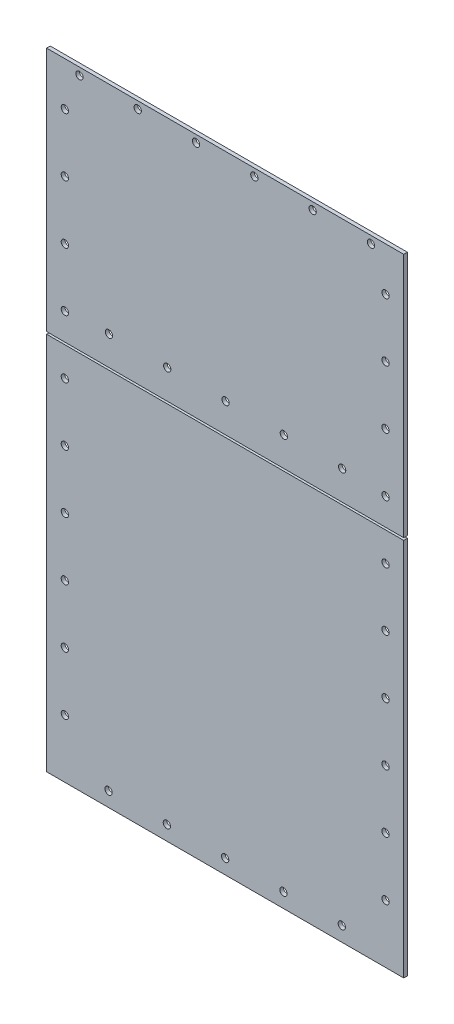
SolidWorks part; units mm, degrees
material "Copper"
ref_plane "Front Plane" through (0, 0, 0) normal (0, 0, 1) x (1, 0, 0)
ref_plane "Top Plane" through (0, 0, 0) normal (0, 1, 0) x (1, 0, 0)
ref_plane "Right Plane" through (0, 0, 0) normal (1, 0, 0) x (0, 0, -1)
sketch "Sketch1" plane through (0, 0, 0) normal (0, 0, 1) x (1, 0, 0)
  line L0 (0, -106.95) -> (155.58, -106.95)
  line L1 (0, 0) -> (155.58, 0)
  line L2 (0, 0) -> (0, -273.05)
  line L3 (0, -273.05) -> (155.58, -273.05)
  line L4 (155.58, 0) -> (155.58, -273.05)
  line L5 (0, -107.95) -> (155.58, -107.95)
  circle A0 centre (7.94, -19.05) radius 1.5875
  circle A1 centre (147.64, -19.05) radius 1.5875
  circle A2 centre (147.64, -44.45) radius 1.5875
  circle A3 centre (147.64, -69.85) radius 1.5875
  circle A4 centre (147.64, -95.25) radius 1.5875
  circle A5 centre (147.64, -120.65) radius 1.5875
  circle A6 centre (147.64, -146.05) radius 1.5875
  circle A7 centre (147.64, -171.45) radius 1.5875
  circle A8 centre (147.64, -196.85) radius 1.5875
  circle A9 centre (147.64, -222.25) radius 1.5875
  circle A10 centre (147.64, -247.65) radius 1.5875
  circle A11 centre (7.94, -44.45) radius 1.5875
  circle A12 centre (7.94, -69.85) radius 1.5875
  circle A13 centre (7.94, -95.25) radius 1.5875
  circle A14 centre (7.94, -120.65) radius 1.5875
  circle A15 centre (7.94, -146.05) radius 1.5875
  circle A16 centre (7.94, -171.45) radius 1.5875
  circle A17 centre (7.94, -196.85) radius 1.5875
  circle A18 centre (7.94, -222.25) radius 1.5875
  circle A19 centre (7.94, -247.65) radius 1.5875
  circle A20 centre (14.29, -3.175) radius 1.5875
  circle A21 centre (39.69, -3.175) radius 1.5875
  circle A22 centre (65.09, -3.175) radius 1.5875
  circle A23 centre (90.49, -3.175) radius 1.5875
  circle A24 centre (115.89, -3.175) radius 1.5875
  circle A25 centre (141.29, -3.175) radius 1.5875
  circle A26 centre (26.987, -266.7) radius 1.5875
  circle A27 centre (52.387, -266.7) radius 1.5875
  circle A28 centre (77.787, -266.7) radius 1.5875
  circle A29 centre (103.187, -266.7) radius 1.5875
  circle A30 centre (128.587, -266.7) radius 1.5875
  circle A31 centre (27.141, -94.25) radius 1.5875
  circle A32 centre (52.541, -94.25) radius 1.5875
  circle A33 centre (77.941, -94.25) radius 1.5875
  circle A34 centre (103.341, -94.25) radius 1.5875
  circle A35 centre (128.741, -94.25) radius 1.5875
  dimension "D3" = 3.175
  dimension "D1" = 155.58
  dimension "D2" = 273.05
  dimension "D4" = 19.05
  dimension "D5" = 7.94
  dimension "D8" = 25.4
  dimension "D9" = 7.94
  dimension "D10" = 3.175
  dimension "D11" = 14.29
  dimension "D13" = 25.4
  dimension "D14" = 6.35
  dimension "D15" = 26.987
  dimension "D17" = 25.4
  dimension "D18" = 11.7
  dimension "D19" = 1
  dimension "D20" = 12.7
  dimension "D21" = 27.141
  dimension "D23" = 25.4
  dimension "D6" = 2
  dimension "D7" = 10
  dimension "D12" = 6
  dimension "D16" = 5
  dimension "D22" = 5
extrude "Boss-Extrude1" add sketch "Sketch1" along normal blind 1.5875 contours L4 L1 L2 L0 A25 A24 A23 A22 A21 A20 A13 A12 A11 A4 A3 A2 A1 A0 | L4 L0 L2 L3 A30 A29 A28 A27 A26 A19 A18 A17 A16 A15 A14 A10 A9 A8 A7 A6 A5 region at (77.7896, -53.5079, 0) region at (77.79, -190.4056, 0)
equation "\"D9@Sketch1\"=\"D5@Sketch1\""
equation "\"D18@Sketch1\"=\"D8@Sketch1\"/2-1"
